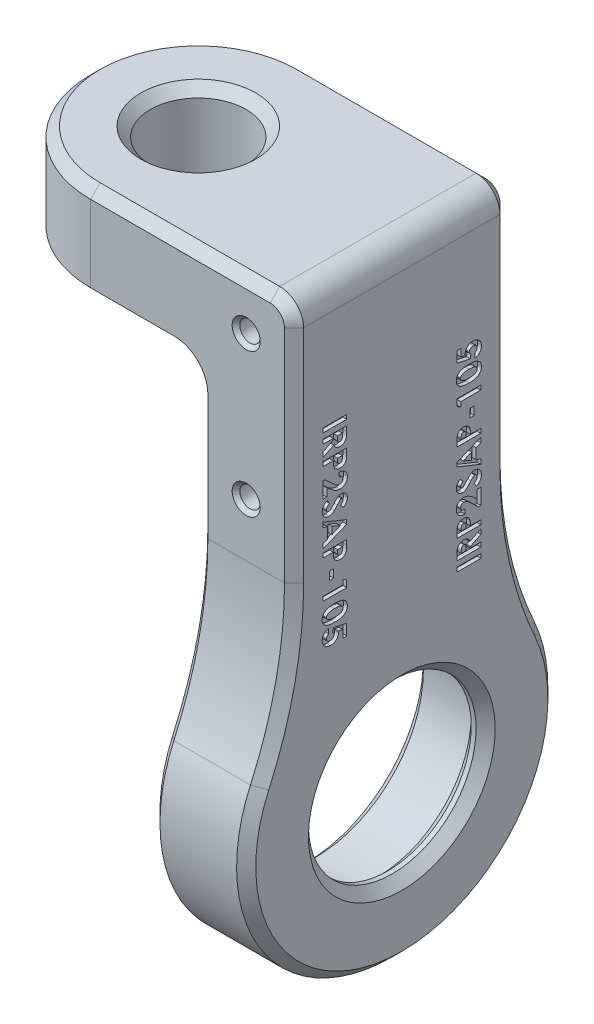
SolidWorks part; units mm, degrees
material "6061-T6 (SS)"
ref_plane "Front" through (0, 0, 0) normal (0, 0, 1) x (1, 0, 0)
ref_plane "Top" through (0, 0, 0) normal (0, 1, 0) x (1, 0, 0)
ref_plane "Right" through (0, 0, 0) normal (1, 0, 0) x (0, 0, -1)
sketch "Sketch1" plane through (0, 0, 0) normal (0, 0, 1) x (1, 0, 0)
  line L0 (0, 0) -> (41.275, 0)
  line L1 (41.275, 0) -> (41.275, -47.625)
  line L2 (41.275, -47.625) -> (41.275, -76.2)
  line L3 (41.275, -76.2) -> (28.575, -76.2)
  line L4 (28.575, -76.2) -> (28.575, -47.625)
  line L5 (28.575, -47.625) -> (28.575, -12.7)
  line L6 (28.575, -12.7) -> (0, -12.7)
  line L7 (0, -12.7) -> (0, 0)
  line L8 (28.575, -30.1625) -> (41.275, -30.1625) construction
  point P2 (0, 0)
  point P10 (0, 0)
  point P11 (74.5512, -39.3997)
  point P13 (34.6772, -15.9206)
  point P14 (0, 0)
  point P15 (0, 0)
  point P17 (76.2, -43.6217)
  dimension "D1" = 12.7
  dimension "D2" = 76.2
  dimension "D3" = 28.575
extrude "Boss-Extrude1" add sketch "Sketch1" along normal blind 28.575
fillet "Fillet1" radius 14.2875 4 edges at (34.925, -76.2, 0) (34.925, -76.2, 28.575) (0, -6.35, 0) (0, -6.35, 28.575)
sketch "Sketch8" plane through (28.575, 0, 0) normal (-1, 0, 0) x (0, 0, 1)
  line L0 (0, -12.7) -> (0, -61.9125) construction
  line L1 (28.575, -12.7) -> (28.575, -61.9125) construction
  line L2 (0, -32.4688) -> (28.575, -32.4688)
  circle A0 centre (14.2875, -61.9125) radius 20.6375
  arc A1 (-4.5156, -53.4065) -> (0, -32.4688) centre (-50.8, -32.4688) ccw
  arc A2 (28.575, -32.4688) -> (33.0906, -53.4065) centre (79.375, -32.4688) ccw
  line M2 (0, -12.7) -> (0, -61.9125)
  arc M3 (0, -61.9125) -> (14.2875, -76.2) centre (14.2875, -61.9125) ccw
  arc M4 (14.2875, -76.2) -> (28.575, -61.9125) centre (14.2875, -61.9125) ccw
  line M5 (28.575, -61.9125) -> (28.575, -12.7)
  dimension "D1" = 41.275
  dimension "D2" = 50.8
extrude "Boss-Extrude2" add sketch "Sketch8" against normal blind 12.7 contours A0 M2 M5 M4 M3 | A2 A0 M5 | A1 A0 M2 region at (28.575, -44.9358, -1.0448) region at (28.575, -44.9358, 29.6198) region at (28.575, -50.312, -2.1184)
fillet "Fillet2" radius 3.175 2 edges at (41.275, 0, 14.2875) (28.575, -12.7, 14.2875)
chamfer "Chamfer1" distance 1.27 angle 45 22 edges at (27.6451, -13.6299, 0) (19.8438, -12.7, 0) (28.575, -24.1719, 0) (4.1847, -12.7, 4.1847) (4.1847, -12.7, 24.3903) (19.8438, -12.7, 28.575) (27.6451, -13.6299, 28.575) (28.575, -24.1719, 28.575) (40.3451, -0.9299, 0) (41.275, -17.8219, 0) (26.1938, 0, 0) (4.1847, 0, 4.1847) (4.1847, 0, 24.3903) (26.1938, 0, 28.575) (40.3451, -0.9299, 28.575) (41.275, -17.8219, 28.575) (28.575, -43.1783, -1.1417) (28.575, -82.55, 14.2875) (28.575, -43.1783, 29.7167) (41.275, -43.1783, -1.1417) (41.275, -82.55, 14.2875) (41.275, -43.1783, 29.7167)
sketch "Sketch2" plane through (0, 0, 0) normal (0, 1, 0) x (1, 0, 0)
  circle A0 centre (14.2875, -14.2875) radius 6.35
  dimension "D1" = 12.7
extrude "Cut-Extrude1" cut sketch "Sketch2" against normal through all
ref_plane "Plane1" through (20.6375, -20.6375, 0) normal (-0.7071, 0.7071, 0) x (0, 0, 1)
sketch "Sketch3" plane through (41.275, 0, 0) normal (1, 0, 0) x (0, 0, -1)
  line L0 (-24.765, -3.175) -> (-24.765, -53.93) construction
  line L1 (-1.27, -3.175) -> (-27.305, -3.175) construction
  line L3 (-3.81, -3.175) -> (-3.81, -53.93) construction
  line L4 (-27.305, -3.175) -> (-27.305, -32.4688) construction
  line L5 (-1.27, -32.4688) -> (-1.27, -3.175) construction
  text T0 "<b>IRP2SAP-105</b>"
  text T1 "<b>IRP2SAP-105</b>"
  point P4 (0, 0)
  point P5 (0, 0)
  point P13 (0, 0)
  dimension "D1" = 2.54
  dimension "D2" = 2.54
extrude "Cut-Extrude2" cut sketch "Sketch3" against normal blind 0.508
hole_wizard "#6-32 Tapped Hole1" positions "Sketch4" profile "Sketch5" tap size "#6-32" standard "ANSI Inch" end condition through all
sketch "Sketch4" plane through (0, 0, 28.575) normal (0, 0, 1) x (1, 0, 0)
  line L0 (40.005, -17.8219) -> (29.845, -17.8219) construction
  line L1 (40.005, -32.4688) -> (40.005, -3.175) construction
  line L4 (34.925, -6.35) -> (34.925, -15.875) construction
  line L5 (34.925, -15.875) -> (34.925, -25.4) construction
  line L7 (29.845, -15.875) -> (29.845, -32.4688) construction
  line L8 (38.1, 0) -> (14.2875, 0) construction
  point P0 (34.925, -6.35)
  point P2 (34.925, -25.4)
  point P17 (0, 0)
  point P20 (0, 0)
  point P21 (0, 0)
  point P22 (25.0407, -17.8219)
  point P23 (25.3105, -22.9254)
  point P24 (34.925, -17.8219)
  dimension "D1" = 9.525
  dimension "D2" = 6.35
sketch "Sketch5" plane through (34.925, -6.35, 28.575) normal (1, 0, 0) x (0, -1, 0)
  line L0 (0, 0) -> (0, 34.925)
  line L1 (0, 34.925) -> (1.3525, 34.925)
  line L2 (1.3525, 34.925) -> (1.3525, 0)
  line L5 (1.3525, 0) -> (0, 0)
  line L11 (0, -6.35) -> (0, 107.95) construction
  dimension "Thru Tap Drill Dia." = 2.7051
  dimension "Thru Tap Drill Depth" = 34.925
cosmetic thread "Hole Thread1" parameters "D2"=3.5052
cosmetic thread "Hole Thread2" parameters "D2"=3.5052
chamfer "Chamfer3" distance 0.508 angle 45 4 edges at (36.2775, -25.4, 28.575) (33.5725, -25.4, 0) (36.2775, -6.35, 28.575) (33.5725, -6.35, 0)
sketch "Sketch6" plane through (41.275, 0, 0) normal (1, 0, 0) x (0, 0, -1)
  circle A0 centre (-14.2875, -61.9125) radius 11.1125
  arc A1 (-31.9334, -53.93) -> (3.3584, -53.93) centre (-14.2875, -61.9125) ccw construction
  point P3 (0, 0)
  dimension "D1" = 22.225
extrude "Cut-Extrude3" cut sketch "Sketch6" against normal through all
sketch "Sketch9" plane through (28.575, 0, 0) normal (1, 0, 0) x (0, 0, -1)
  circle A0 centre (-14.2875, -61.9125) radius 14.2875
  circle A1 centre (-14.2875, -61.9125) radius 20.6375 construction
  point P3 (0, 0)
  dimension "D1" = 28.575
extrude "Cut-Extrude4" cut sketch "Sketch9" along normal blind 9.525
chamfer "Chamfer4" distance 1.27 angle 45 5 edges at (7.9375, -12.7, 14.2875) (14.2875, 0, 20.6375) (41.275, -50.8, 14.2875) (38.1, -50.8, 14.2875) (28.575, -47.625, 14.2875)
